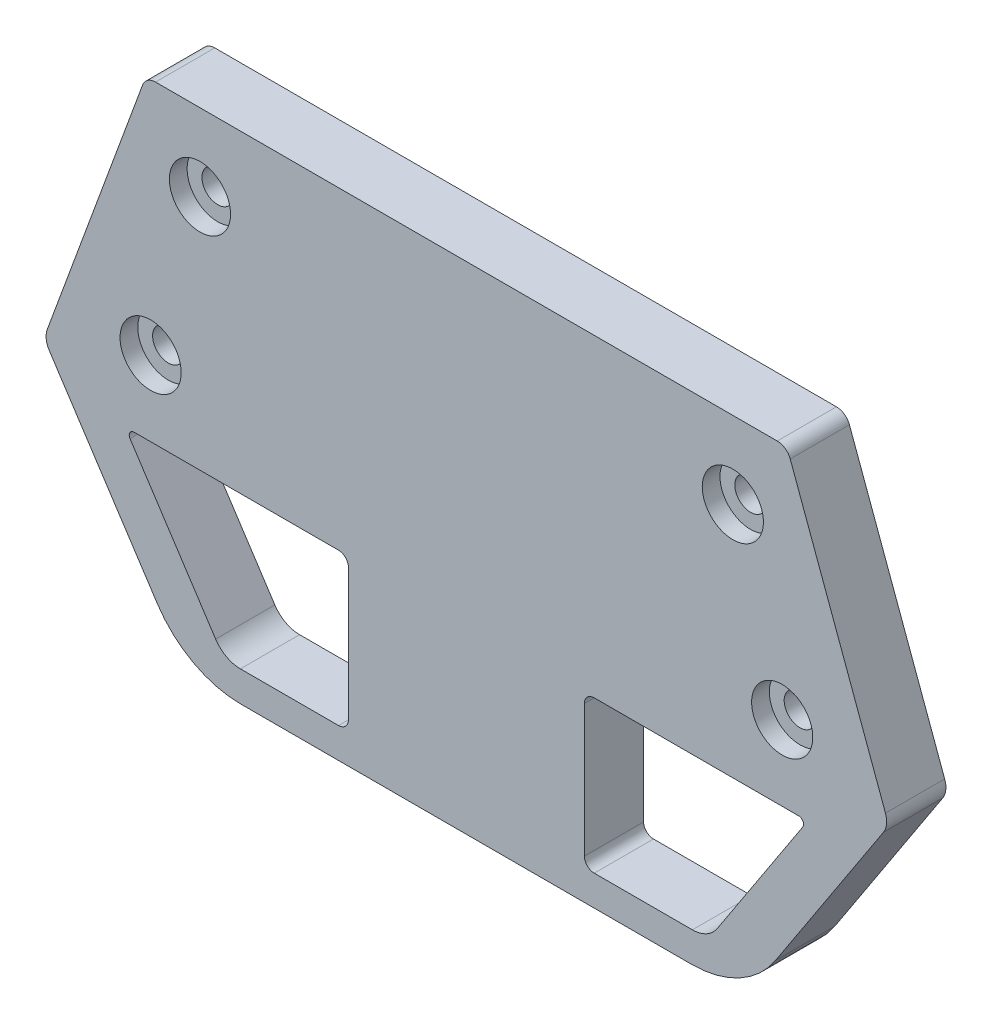
SolidWorks part; units mm, degrees
ref_plane "Front Plane" through (0, 0, 0) normal (0, 0, 1) x (1, 0, 0)
ref_plane "Top Plane" through (0, 0, 0) normal (0, 1, 0) x (1, 0, 0)
ref_plane "Right Plane" through (0, 0, 0) normal (1, 0, 0) x (0, 0, -1)
sketch "Sketch2" plane through (0, 0, 0) normal (0, 0, 1) x (1, 0, 0)
  line L0 (0, -44.7145) -> (0, 43.9236) construction
  line L3 (-53.9331, -0.3154) -> (-41.6738, 33.03)
  line L5 (-53.6746, -2.5826) -> (-39.7807, -23.8164)
  line L8 (-28.9986, -29.6465) -> (28.9986, -29.6465)
  line L9 (-40.005, 34.1945) -> (40.005, 34.1945)
  line L10 (53.6746, -2.5826) -> (39.7807, -23.8164)
  line L11 (53.9331, -0.3154) -> (41.6738, 33.03)
  arc A1 (-40.005, 34.1945) -> (-41.6738, 33.03) centre (-40.005, 32.4165) ccw
  arc A6 (-28.9986, -29.6465) -> (-39.7807, -23.8164) centre (-28.9986, -16.7614) cw
  arc A8 (-53.6746, -2.5826) -> (-53.9331, -0.3154) centre (-51.5491, -1.1919) cw
  arc A10 (53.6746, -2.5826) -> (53.9331, -0.3154) centre (51.5491, -1.1919) ccw
  arc A11 (28.9986, -29.6465) -> (39.7807, -23.8164) centre (28.9986, -16.7614) ccw
  arc A13 (40.005, 34.1945) -> (41.6738, 33.03) centre (40.005, 32.4165) cw
  point P4 (0, 57.6776)
  point P9 (0, 19.5776)
  point P12 (54.3738, -1.514)
  point P13 (0, -29.6465)
  point P19 (-35.9659, -29.6465)
  point P20 (0, -3.9055)
  point P28 (-54.3738, -1.514)
  point P33 (0, 34.1945)
  point P34 (35.9659, -29.6465)
  dimension "D2" = 1.778
  dimension "D3" = 12.8851
  dimension "D6" = 28.9986
  dimension "D4" = 2.54
  dimension "D7" = 35.9659
  dimension "D8" = 40.005
  dimension "D9" = 41.6738
  dimension "D10" = 51.5491
  dimension "D12" = 19.5776
  dimension "D13" = 32.4165
  dimension "D14" = 57.6776
extrude "Boss-Extrude1" add sketch "Sketch2" along normal blind 7.62
sketch "Sketch6" plane through (0, 0, 7.62) normal (0, 0, 1) x (1, 0, 0)
  line L0 (0, -25.1696) -> (0, 28.2164) construction
  line L3 (-43.2885, -7.1893) -> (-32.2734, -24.0235)
  line L4 (-53.6746, -2.5826) -> (-39.7807, -23.8164) construction
  line L5 (-54.0728, -1.4797) -> (0, -1.4797) construction
  line L6 (-42.7572, -6.2066) -> (-16.453, -6.2066)
  line L7 (-15.183, -7.4766) -> (-15.183, -24.4774)
  line L13 (-29.0853, -25.7474) -> (-16.453, -25.7474)
  line L14 (43.2885, -7.1893) -> (32.2734, -24.0235)
  line L17 (29.0853, -25.7474) -> (16.453, -25.7474)
  line L18 (15.183, -7.4766) -> (15.183, -24.4774)
  line L19 (42.7572, -6.2066) -> (16.453, -6.2066)
  line L20 (-11.43, -10.9992) -> (-11.43, -29.6465) construction
  line L21 (-28.9986, -29.6465) -> (28.9986, -29.6465) construction
  arc A3 (-53.9331, -0.3154) -> (-53.6746, -2.5826) centre (-51.5491, -1.1919) ccw construction
  arc A6 (-15.183, -7.4766) -> (-16.453, -6.2066) centre (-16.453, -7.4766) ccw
  arc A7 (-42.7572, -6.2066) -> (-43.2885, -7.1893) centre (-42.7572, -6.8416) ccw
  arc A12 (-29.0853, -25.7474) -> (-32.2734, -24.0235) centre (-29.0853, -21.9374) cw
  arc A13 (-15.183, -24.4774) -> (-16.453, -25.7474) centre (-16.453, -24.4774) cw
  arc A14 (42.7572, -6.2066) -> (43.2885, -7.1893) centre (42.7572, -6.8416) cw
  arc A15 (29.0853, -25.7474) -> (32.2734, -24.0235) centre (29.0853, -21.9374) ccw
  arc A16 (15.183, -24.4774) -> (16.453, -25.7474) centre (16.453, -24.4774) ccw
  arc A17 (15.183, -7.4766) -> (16.453, -6.2066) centre (16.453, -7.4766) cw
  dimension "D1" = 3.81
  dimension "D2" = 1.27
  dimension "D3" = 26.613
  dimension "D4" = 0.635
  dimension "D5" = 40.5153
  dimension "D6" = 54.1872
  dimension "D7" = 3.8991
extrude "Cut-Extrude4" cut sketch "Sketch6" against normal through all
sketch "Sketch8" plane through (0, 0, 7.62) normal (0, 0, 1) x (1, 0, 0)
  line L0 (0, 24.5882) -> (0, -31.804) construction
  line L1 (-16.453, -6.2066) -> (-42.7572, -6.2066) construction
  circle A0 centre (-40.64, 3.4454) radius 2.032
  circle A1 centre (-34.29, 24.2734) radius 2.032
  circle A2 centre (40.64, 3.4454) radius 2.032
  circle A3 centre (34.29, 24.2734) radius 2.032
  dimension "D1" = 4.064
  dimension "D2" = 4.064
  dimension "D3" = 40.64
  dimension "D4" = 34.29
  dimension "D5" = 9.652
  dimension "D6" = 30.48
extrude "Cut-Extrude6" cut sketch "Sketch8" against normal through all
sketch "Sketch9" plane through (0, -29.6465, 0) normal (0, -1, 0) x (1, 0, 0)
  line L0 (0, -14.4205) -> (0, 21.768) construction
  line L1 (-28.9986, 3.81) -> (28.9986, 3.81) construction
  line L2 (-28.9986, 7.62) -> (-28.9986, 0) construction
  line L3 (28.9986, 7.62) -> (28.9986, 0) construction
  circle A0 centre (0, 3.81) radius 2.032
  dimension "D1" = 4.064
extrude "Cut-Extrude7" cut sketch "Sketch9" against normal blind 25.4
sketch "Sketch11" plane through (0, 0, 7.62) normal (0, 0, 1) x (1, 0, 0)
  line L0 (0, 31.297) -> (0, -23.5528) construction
  circle A0 centre (-34.29, 24.2734) radius 3.937
  circle A1 centre (-40.64, 3.4454) radius 3.937
  circle A2 centre (40.64, 3.4454) radius 3.937
  circle A3 centre (34.29, 24.2734) radius 3.937
  dimension "D1" = 7.874
  dimension "D2" = 7.874
extrude "Cut-Extrude9" cut sketch "Sketch11" against normal blind 2.286
